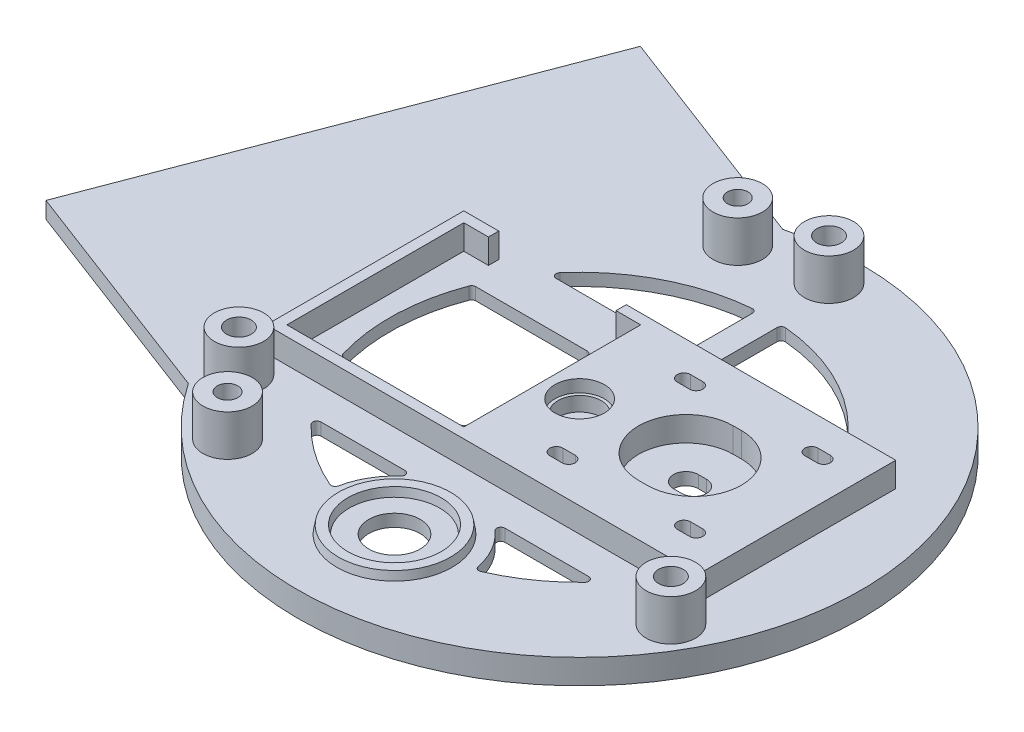
SolidWorks part; units mm, degrees
material "ABS"
ref_plane "Front Plane" through (0, 0, 0) normal (0, 0, 1) x (1, 0, 0)
ref_plane "Top Plane" through (0, 0, 0) normal (0, 1, 0) x (1, 0, 0)
ref_plane "Right Plane" through (0, 0, 0) normal (1, 0, 0) x (0, 0, -1)
sketch "Sketch1" plane through (0, 0, 0) normal (0, 0, 1) x (1, 0, 0)
  line L0 (0, 0) -> (68.5, 0)
  line L1 (68.5, 0) -> (68.5, -6)
  line L2 (68.5, -6) -> (66.5, -6)
  line L3 (66.5, -6) -> (66.5, -3)
  line L5 (53.5, -3) -> (53.5, -6)
  line L6 (53.5, -6) -> (50.5, -6)
  line L7 (50.5, -6) -> (50.5, -3)
  line L8 (50.5, -3) -> (8, -3)
  line L9 (8, -3) -> (8, -8)
  line L10 (8, -8) -> (0, -8)
  line L11 (0, -8) -> (0, 0)
  line L12 (62.3516, -3) -> (66.5, -3)
  line L13 (57.6484, -3) -> (53.5, -3)
  arc A0 (62.3516, -3) -> (57.6484, -3) centre (60, -6.6) ccw
  point P4 (67.5, -6)
  dimension "D2" = 4.3
  dimension "D1" = 60
  dimension "D3" = 6.5
  dimension "D4" = 3
  dimension "D5" = 6.5
  dimension "D6" = 3
  dimension "D7" = 2
  dimension "D8" = 50.5
  dimension "D9" = 0.6
  dimension "D10" = 8
  dimension "D11" = 8
revolve "Revolve1" add sketch "Sketch1" angle 360 about L11
sketch "Sketch2" plane through (0, 0, 0) normal (0, 1, 0) x (1, 0, 0)
  line L0 (-52.5, -30.3109) -> (0, 60.6218) construction
  line L1 (0, 60.6218) -> (52.5, -30.3109) construction
  line L2 (52.5, -30.3109) -> (-52.5, -30.3109) construction
  line L3 (0, 0) -> (0, 60.6218) construction
  line L4 (0, 0) -> (52.5, -30.3109) construction
  line L5 (0, 0) -> (-52.5, -30.3109) construction
  line L6 (0, 0) -> (0, -45) construction
  line L7 (-40.2731, -45.3109) -> (-40.2731, -30.3109) construction
  line L8 (-19.1038, 57.533) -> (-6.1134, 50.033) construction
  circle A0 centre (0, 60.6218) radius 6
  circle A1 centre (0, 60.6218) radius 3
  circle A2 centre (52.5, -30.3109) radius 6
  circle A3 centre (-52.5, -30.3109) radius 6
  circle A4 centre (-52.5, -30.3109) radius 3
  circle A5 centre (52.5, -30.3109) radius 3
  circle A6 centre (0, -45) radius 6.25 construction
  arc A7 (0, 60.6218) -> (-24.7136, -55.3555) centre (0, 0) ccw construction
  circle A8 centre (-40.2731, -45.3109) radius 6
  circle A9 centre (-19.1038, 57.533) radius 6
  circle A10 centre (-40.2731, -45.3109) radius 2.5
  circle A11 centre (-19.1038, 57.533) radius 2.5
  arc A12 (15.6635, -19.9954) -> (14.3368, 20.9671) centre (0, 0) ccw construction
  dimension "D2" = 12
  dimension "D3" = 6
  dimension "D5" = 12.5
  dimension "D6" = 12
  dimension "D8" = 5
  dimension "D9" = 25.4
  dimension "D1" = 105
  dimension "D4" = 45
  dimension "D7" = 15
extrude "Boss-Extrude1" add sketch "Sketch2" along normal blind 10
sketch "Sketch3" plane through (0, 0, 0) normal (0, 1, 0) x (1, 0, 0)
  circle A0 centre (0, -45) radius 6.25
  circle A1 centre (0, -45) radius 6.25 construction
extrude "Cut-Extrude1" cut sketch "Sketch3" against normal blind 10
sketch "Sketch4" plane through (0, 0, 0) normal (0, 1, 0) x (1, 0, 0)
  circle A0 centre (0, -45) radius 11
  circle A1 centre (0, -45) radius 14
  dimension "D1" = 22
  dimension "D2" = 28
extrude "Boss-Extrude2" add sketch "Sketch4" along normal blind 2 draft 10
sketch "Sketch5" plane through (0, 0, 0) normal (0, 1, 0) x (1, 0, 0)
  line L0 (51.3563, -22.5103) -> (51.3563, 25.4897)
  line L1 (51.3563, -22.5103) -> (-53.6437, -22.5103)
  line L2 (51.3563, 25.4897) -> (-53.6437, 25.4897) construction
  line L3 (-53.6437, -22.5103) -> (-53.6437, 25.4897)
  line L4 (-51.1437, 22.9897) -> (-45.1437, 22.9897)
  line L5 (-53.6437, 1.4897) -> (51.3563, 1.4897) construction
  line L6 (25.3563, 1.4897) -> (25.3563, 25.4897) construction
  line L7 (26.3563, 1.4897) -> (24.3563, 1.4897) construction
  line L8 (26.3563, -10.0103) -> (24.3563, -10.0103)
  line L9 (26.3563, 12.9897) -> (24.3563, 12.9897)
  line L10 (-45.1437, 22.9897) -> (-45.1437, 25.4897)
  line L11 (-51.1437, -20.0103) -> (-51.1437, 22.9897)
  line L12 (-51.1437, 22.9897) -> (-8.1437, 22.9897) construction
  line L13 (-8.1437, 22.9897) -> (-8.1437, -20.0103)
  line L14 (-8.1437, -20.0103) -> (-51.1437, -20.0103)
  line L15 (-45.1437, 25.4897) -> (-53.6437, 25.4897)
  line L16 (-8.1437, 22.9897) -> (-14.1437, 22.9897)
  line L17 (-14.1437, 22.9897) -> (-14.1437, 25.4897)
  line L18 (-14.1437, 25.4897) -> (51.3563, 25.4897)
  arc A1 (26.3563, -10.0103) -> (26.3563, 12.9897) centre (26.3563, 1.4897) ccw
  arc A2 (24.3563, 12.9897) -> (24.3563, -10.0103) centre (24.3563, 1.4897) ccw
  arc A3 (15.6635, -19.9954) -> (14.3368, 20.9671) centre (0, 0) ccw construction
  point P10 (25.3563, 1.4897)
  point P18 (-8.1437, 1.4897)
  dimension "D3" = 23
  dimension "D1" = 48
  dimension "D2" = 105
  dimension "D4" = 2
  dimension "D5" = 26
  dimension "D6" = 2.5
  dimension "D7" = 43
  dimension "D8" = 43
  dimension "D9" = 6
  dimension "D10" = 6
extrude "Boss-Extrude3" add sketch "Sketch5" along normal blind 6
sketch "Sketch12" plane through (0, 0, 0) normal (0, 1, 0) x (1, 0, 0)
  line L0 (0, 60.6218) -> (-40.2731, -45.3109) construction
  line L1 (-56.7747, -38.326) -> (-112.6257, -17.0928)
  line L2 (-112.6257, -17.0928) -> (-72.8252, 87.5969)
  line L3 (-72.8252, 87.5969) -> (-16.9742, 66.3636)
  line L4 (0, 0) -> (-92.7255, 35.252) construction
  circle A0 centre (0, 0) radius 68.5 construction
  arc A1 (-56.7747, -38.326) -> (-16.9742, 66.3636) centre (0, 0) cw
  point P8 (-20.1366, 7.6554)
  point P17 (0, 0)
  point P18 (0, 0)
  dimension "D2" = 40
  dimension "D1" = 112
extrude "Boss-Extrude5" add sketch "Sketch12" against normal blind 4
sketch "Sketch6" plane through (0, 6, 0) normal (0, 1, 0) x (1, 0, 0)
  line L0 (40.8563, -14.0103) -> (40.8563, 16.9897) construction
  line L1 (40.8563, -14.0103) -> (9.8563, -14.0103) construction
  line L2 (40.8563, 16.9897) -> (9.8563, 16.9897) construction
  line L3 (9.8563, -14.0103) -> (9.8563, 16.9897) construction
  line L4 (40.8563, -14.0103) -> (9.8563, 16.9897) construction
  line L5 (40.8563, 16.9897) -> (9.8563, -14.0103) construction
  line L6 (25.3563, 1.4897) -> (25.3563, 25.4897) construction
  line L7 (11.3563, -14.0103) -> (8.3563, -14.0103) construction
  line L8 (11.3563, -15.6103) -> (8.3563, -15.6103)
  line L9 (11.3563, -12.4103) -> (8.3563, -12.4103)
  line L10 (42.3563, -14.0103) -> (39.3563, -14.0103) construction
  line L11 (42.3563, -15.6103) -> (39.3563, -15.6103)
  line L12 (42.3563, -12.4103) -> (39.3563, -12.4103)
  line L13 (42.3563, 16.9897) -> (39.3563, 16.9897) construction
  line L14 (42.3563, 15.3897) -> (39.3563, 15.3897)
  line L15 (42.3563, 18.5897) -> (39.3563, 18.5897)
  line L16 (11.3563, 16.9897) -> (8.3563, 16.9897) construction
  line L17 (11.3563, 15.3897) -> (8.3563, 15.3897)
  line L18 (11.3563, 18.5897) -> (8.3563, 18.5897)
  arc A0 (11.3563, -15.6103) -> (11.3563, -12.4103) centre (11.3563, -14.0103) ccw
  arc A1 (8.3563, -12.4103) -> (8.3563, -15.6103) centre (8.3563, -14.0103) ccw
  arc A2 (42.3563, -15.6103) -> (42.3563, -12.4103) centre (42.3563, -14.0103) ccw
  arc A3 (39.3563, -12.4103) -> (39.3563, -15.6103) centre (39.3563, -14.0103) ccw
  arc A4 (42.3563, 15.3897) -> (42.3563, 18.5897) centre (42.3563, 16.9897) ccw
  arc A5 (39.3563, 18.5897) -> (39.3563, 15.3897) centre (39.3563, 16.9897) ccw
  arc A6 (11.3563, 15.3897) -> (11.3563, 18.5897) centre (11.3563, 16.9897) ccw
  arc A7 (8.3563, 18.5897) -> (8.3563, 15.3897) centre (8.3563, 16.9897) ccw
  point P1 (25.3563, 1.4897)
  point P2 (25.3563, 16.9897)
  point P11 (9.8563, -14.0103)
  point P21 (40.8563, -14.0103)
  point P28 (40.8563, 16.9897)
  point P35 (9.8563, 16.9897)
  dimension "D2" = 1.6
  dimension "D1" = 31
  dimension "D3" = 3
  dimension "D4" = 2
  dimension "D5" = 2
extrude "Cut-Extrude2" cut sketch "Sketch6" against normal through all
sketch "Sketch7" plane through (0, 0, 0) normal (0, 1, 0) x (1, 0, 0)
  line L0 (26.3563, 1.4897) -> (24.3563, 1.4897) construction
  line L1 (26.3563, -1.5103) -> (24.3563, -1.5103)
  line L2 (26.3563, 4.4897) -> (24.3563, 4.4897)
  arc A0 (26.3563, -1.5103) -> (26.3563, 4.4897) centre (26.3563, 1.4897) ccw
  arc A1 (24.3563, 4.4897) -> (24.3563, -1.5103) centre (24.3563, 1.4897) ccw
  point P2 (25.3563, 1.4897)
  dimension "D1" = 3
extrude "Cut-Extrude3" cut sketch "Sketch7" against normal through all
sketch "Sketch8" plane through (0, 6, 0) normal (0, 1, 0) x (1, 0, 0)
  circle A0 centre (0, 0) radius 1.75
  dimension "D1" = 3.5
extrude "Cut-Extrude4" cut sketch "Sketch8" against normal through all
chamfer "Chamfer1" distance 2 angle 45 16 edges at (37.7563, -3, 14.0103) (40.8563, -3, 12.4103) (40.8563, -3, 15.6103) (43.9563, -3, 14.0103) (37.7563, -3, -16.9897) (40.8563, -3, -18.5897) (40.8563, -3, -15.3897) (43.9563, -3, -16.9897) (6.7563, -3, -16.9897) (9.8563, -3, -18.5897) (9.8563, -3, -15.3897) (12.9563, -3, -16.9897) (6.7563, -3, 14.0103) (9.8563, -3, 12.4103) (9.8563, -3, 15.6103) (12.9563, -3, 14.0103)
sketch "Sketch9" plane through (0, 6, 0) normal (0, 1, 0) x (1, 0, 0)
  circle A0 centre (0, 0) radius 5.25
  dimension "D1" = 10.5
extrude "Cut-Extrude5" cut sketch "Sketch9" against normal blind 6.5
sketch "Sketch10" plane through (0, 6, 0) normal (0, 1, 0) x (1, 0, 0)
  circle A0 centre (0, 0) radius 6
  dimension "D1" = 12
extrude "Cut-Extrude6" cut sketch "Sketch10" against normal blind 3
sketch "Sketch11" plane through (0, 0, 0) normal (0, 1, 0) x (1, 0, 0)
  line L0 (-14.1437, -13.0103) -> (-14.1437, 15.9897)
  line L1 (-15.1437, 16.9897) -> (-42.2431, 16.9897)
  line L2 (-15.1437, -14.0103) -> (-43.2536, -14.0103)
  line L3 (-8.1437, 22.9897) -> (-8.1437, -20.0103) construction
  line L4 (-8.1437, -20.0103) -> (-51.1437, -20.0103) construction
  line L5 (-51.1437, 22.9897) -> (-8.1437, 22.9897) construction
  line L6 (-36.3293, 28.4897) -> (36.3293, 28.4897) construction
  line L7 (51.3563, 25.4897) -> (-53.6437, 25.4897) construction
  line L8 (3, 29.4897) -> (3, 44.9905)
  line L9 (-3, 29.4897) -> (-3, 44.9905)
  line L10 (-34.2126, 28.4897) -> (-4, 28.4897)
  line L11 (4, 28.4897) -> (34.2126, 28.4897)
  line L12 (52.5, -30.3109) -> (-52.5, -30.3109) construction
  line L13 (-32.5542, -30.3109) -> (-12.1463, -30.3109)
  line L14 (12.1463, -30.3109) -> (32.5542, -30.3109)
  arc A0 (-43.1783, 16.3437) -> (-44.2113, -13.2984) centre (0, 0) ccw
  arc A1 (-36.3293, 28.4897) -> (36.3293, 28.4897) centre (0, 0) cw construction
  arc A2 (-4.0886, 45.9866) -> (-34.9701, 30.1426) centre (0, 0) ccw
  arc A3 (34.9701, 30.1426) -> (4.0886, 45.9866) centre (0, 0) ccw
  arc A4 (33.2749, -32.0041) -> (18.3502, -42.3645) centre (0, 0) cw
  arc A5 (-18.3502, -42.3645) -> (-33.2749, -32.0041) centre (0, 0) cw
  arc A6 (16.9717, -41.6411) -> (11.4826, -32.0589) centre (0, -45) ccw
  arc A7 (-16.9717, -41.6411) -> (-11.4826, -32.0589) centre (0, -45) cw
  arc A8 (33.2749, -32.0041) -> (32.5542, -30.3109) centre (32.5542, -31.3109) ccw
  arc A9 (-33.2749, -32.0041) -> (-32.5542, -30.3109) centre (-32.5542, -31.3109) cw
  arc A10 (18.3502, -42.3645) -> (16.9717, -41.6411) centre (17.9527, -41.4469) cw
  arc A11 (-18.3502, -42.3645) -> (-16.9717, -41.6411) centre (-17.9527, -41.4469) ccw
  arc A12 (11.4826, -32.0589) -> (12.1463, -30.3109) centre (12.1463, -31.3109) cw
  arc A13 (-11.4826, -32.0589) -> (-12.1463, -30.3109) centre (-12.1463, -31.3109) ccw
  arc A14 (-14.1437, -13.0103) -> (-15.1437, -14.0103) centre (-15.1437, -13.0103) cw
  arc A15 (-14.1437, 15.9897) -> (-15.1437, 16.9897) centre (-15.1437, 15.9897) ccw
  arc A16 (3, 29.4897) -> (4, 28.4897) centre (4, 29.4897) ccw
  arc A17 (-3, 29.4897) -> (-4, 28.4897) centre (-4, 29.4897) cw
  arc A18 (-43.2536, -14.0103) -> (-44.2113, -13.2984) centre (-43.2536, -13.0103) cw
  arc A19 (-42.2431, 16.9897) -> (-43.1783, 16.3437) centre (-42.2431, 15.9897) ccw
  arc A20 (34.2126, 28.4897) -> (34.9701, 30.1426) centre (34.2126, 29.4897) ccw
  arc A21 (3, 44.9905) -> (4.0886, 45.9866) centre (4, 44.9905) cw
  arc A22 (-3, 44.9905) -> (-4.0886, 45.9866) centre (-4, 44.9905) ccw
  arc A23 (-34.2126, 28.4897) -> (-34.9701, 30.1426) centre (-34.2126, 29.4897) cw
  point P31 (0, 0)
  point P32 (0, 0)
  point P33 (0, 0)
  point P34 (0, 0)
  point P35 (0, 0)
  point P37 (34.8243, -30.3109)
  point P40 (-34.8243, -30.3109)
  point P47 (9.1407, -30.3109)
  point P50 (-9.1407, -30.3109)
  point P57 (3, 28.4897)
  point P60 (-3, 28.4897)
  point P70 (3, 46.0704)
  point P73 (-3, 46.0704)
  dimension "D4" = 3
  dimension "D5" = 6
  dimension "D6" = 1
  dimension "D1" = 6
  dimension "D2" = 6
  dimension "D3" = 6
extrude "Cut-Extrude7" cut sketch "Sketch11" against normal through all
